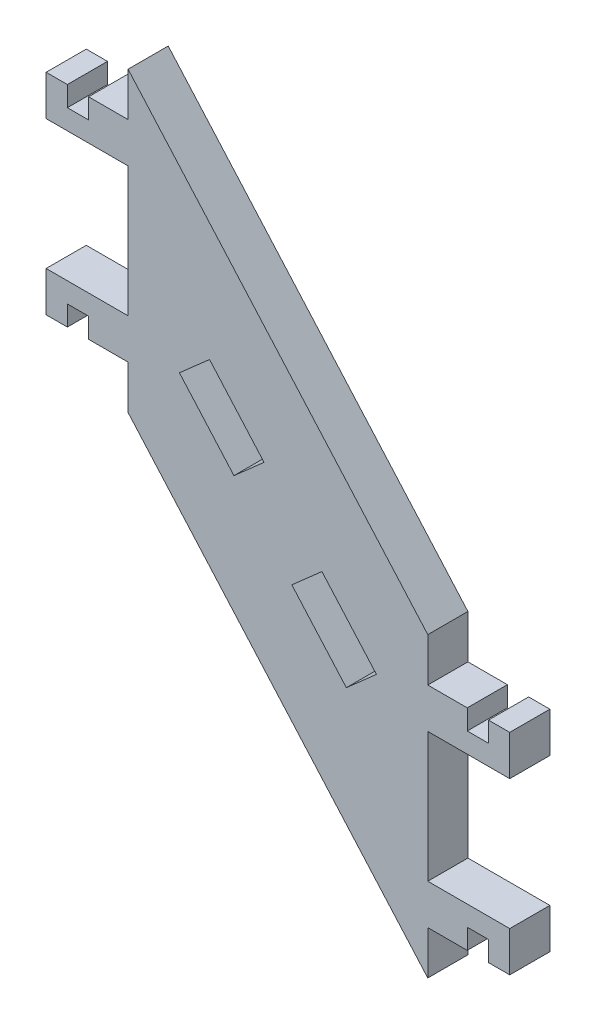
SolidWorks part; units mm, degrees
ref_plane "Front Plane" through (0, 0, 0) normal (0, 0, 1) x (1, 0, 0)
ref_plane "Top Plane" through (0, 0, 0) normal (0, 1, 0) x (1, 0, 0)
ref_plane "Right Plane" through (0, 0, 0) normal (1, 0, 0) x (0, 0, -1)
sketch "Sketch1" plane through (0, 0, 0) normal (0, 0, 1) x (1, 0, 0)
  line L0 (-44.8, 73.025) -> (-44.8, 66.5)
  line L1 (-44.8, 28.575) -> (0, -22.225)
  line L2 (0, -22.225) -> (0, -15.7)
  line L3 (0, 22.225) -> (-44.8, 73.025)
  line L4 (-44.8, 66.5) -> (-50.7, 66.5)
  line L5 (-57.05, 66.5) -> (-57.05, 60.5)
  line L6 (-57.05, 60.5) -> (-44.8, 60.5)
  line L7 (-44.8, 73.025) -> (-50.7, 73.025) construction
  line L8 (-50.7, 73.025) -> (-50.7, 28.575) construction
  line L9 (-50.7, 28.575) -> (-44.8, 28.575) construction
  line L10 (-53.875, 66.5) -> (-53.875, 63.5)
  line L11 (-53.875, 63.5) -> (-50.7, 63.5)
  line L12 (-50.7, 63.5) -> (-50.7, 66.5)
  line L13 (-53.875, 66.5) -> (-57.05, 66.5)
  line L14 (-44.8, 50.8) -> (-64.1486, 50.8) construction
  line L15 (-44.8, 35.1) -> (-50.7, 35.1)
  line L16 (-57.05, 41.1) -> (-44.8, 41.1)
  line L17 (-53.875, 35.1) -> (-57.05, 35.1)
  line L18 (-50.7, 38.1) -> (-50.7, 35.1)
  line L19 (-53.875, 38.1) -> (-50.7, 38.1)
  line L20 (-53.875, 35.1) -> (-53.875, 38.1)
  line L21 (-57.05, 35.1) -> (-57.05, 41.1)
  line L22 (-57.05, 63.5) -> (-50.7, 63.5) construction
  line L23 (0, 0) -> (19.05, 0) construction
  line L24 (0, 9.7) -> (12.25, 9.7)
  line L25 (12.25, 9.7) -> (12.25, 15.7)
  line L26 (12.25, 15.7) -> (9.075, 15.7)
  line L27 (9.075, 15.7) -> (9.075, 12.7)
  line L28 (9.075, 12.7) -> (5.9, 12.7)
  line L29 (5.9, 12.7) -> (5.9, 15.7)
  line L30 (5.9, 15.7) -> (0, 15.7)
  line L31 (5.9, -15.7) -> (0, -15.7)
  line L32 (5.9, -12.7) -> (5.9, -15.7)
  line L33 (9.075, -12.7) -> (5.9, -12.7)
  line L34 (9.075, -15.7) -> (9.075, -12.7)
  line L35 (12.25, -15.7) -> (9.075, -15.7)
  line L36 (12.25, -9.7) -> (12.25, -15.7)
  line L37 (0, -9.7) -> (12.25, -9.7)
  line L38 (0, 22.225) -> (5.9, 22.225) construction
  line L39 (5.9, 22.225) -> (5.9, -22.225) construction
  line L40 (5.9, -22.225) -> (0, -22.225) construction
  line L41 (-44.8, 35.1) -> (-44.8, 41.1) construction
  line L42 (-44.8, 60.5) -> (-44.8, 41.1)
  line L43 (-44.8, 35.1) -> (-44.8, 28.575)
  line L44 (0, 15.7) -> (0, 22.225)
  line L45 (0, -9.7) -> (0, 9.7)
  line L46 (-50.8, -31.2865) -> (-44.8, -31.2865) construction
  line L47 (-50.8, -31.2865) -> (-50.8, 31.2865) construction
  line L48 (-50.8, 31.2865) -> (-44.8, 31.2865) construction
  line L49 (-44.8, -31.2865) -> (-44.8, 31.2865) construction
  line L50 (-50.8, -31.2865) -> (-44.8, 31.2865) construction
  line L51 (-50.8, 31.2865) -> (-44.8, -31.2865) construction
  line L52 (0, -31.2865) -> (6, -31.2865) construction
  line L53 (0, -31.2865) -> (0, 31.2865) construction
  line L54 (0, 31.2865) -> (6, 31.2865) construction
  line L55 (6, -31.2865) -> (6, 31.2865) construction
  line L56 (0, -31.2865) -> (6, 31.2865) construction
  line L57 (0, 31.2865) -> (6, -31.2865) construction
  line L58 (-44.8, 60.5) -> (-44.8, 66.5) construction
  point P25 (-47.8, 0)
  point P37 (0, 0)
  point P53 (3, 0)
  point P58 (-44.8, 38.1)
  point P59 (-44.8, 63.5)
  point P60 (12.25, 12.7)
  point P61 (12.25, -12.7)
  dimension "D4" = 5.9
  dimension "D5" = 3.175
  dimension "D6" = 6
  dimension "D8" = 44.45
  dimension "D10" = 6
  dimension "D11" = 5.9
  dimension "D12" = 3.175
  dimension "D13" = 31.4
  dimension "D14" = 3.175
  dimension "D9" = 3.175
  dimension "D18" = 3.175
  dimension "D19" = 6
  dimension "D20" = 6
  dimension "D21" = 50.8
  dimension "D7" = 25.4
  dimension "D15" = 3
  dimension "D16" = 3
  dimension "D17" = 50.8
extrude "Profile" add sketch "Sketch1" along normal blind 6 contours L1 L2 L31 L32 L33 L34 L35 L36 L37 L45 L24 L25 L26 L27 L28 L29 L30 L44 L3 L0 L4 L12 L11 L10 L13 L5 L6 L42 L16 L21 L17 L20 L19 L18 L15 L43
sketch "Sketch2" plane through (0, 0, 6) normal (0, 0, 1) x (1, 0, 0)
  line L0 (-44.8, 50.8) -> (0, 0) construction
  line L1 (-44.8, 60.5) -> (-44.8, 41.1) construction
  line L2 (-32.6241, 41.5291) -> (-37.1242, 37.5605)
  line L3 (-37.1242, 37.5605) -> (-28.9761, 28.3212)
  line L4 (-28.9761, 28.3212) -> (-24.476, 32.2897)
  line L5 (-24.476, 32.2897) -> (-32.6241, 41.5291)
  line L6 (-33.4253, 15.6769) -> (-11.3747, 35.1231) construction
  line L7 (0, 22.225) -> (-44.8, 73.025) construction
  line L8 (-15.8239, 22.4788) -> (-7.6758, 13.2395)
  line L9 (-20.324, 18.5103) -> (-15.8239, 22.4788)
  line L10 (-12.1759, 9.2709) -> (-20.324, 18.5103)
  line L11 (-7.6758, 13.2395) -> (-12.1759, 9.2709)
  line L12 (-37.1242, 37.5605) -> (-24.476, 32.2897) construction
  point P7 (-34.8742, 39.5448)
  point P14 (-22.4, 25.4)
  point P21 (-30.8001, 34.9251)
  dimension "D1" = 6
  dimension "D2" = 12.319
  dimension "D3" = 12.7
extrude "Cut-Extrude1" cut sketch "Sketch2" against normal through all
equation "\"D10@Sketch1\"=\"D6@Sketch1\""
equation "\"D12@Sketch1\"=\"D5@Sketch1\""
equation "\"D18@Sketch1\"=\"D9@Sketch1\""
equation "\"D4@Sketch1\"=6mm-.1mm"
equation "\"D3@Sketch1\"=\"D7@Sketch1\""
equation "\"D11@Sketch1\"=\"D4@Sketch1\""
equation "\"D15@Sketch1\"=\"D16@Sketch1\""
equation "\"D1@Sketch2\"=6mm"
